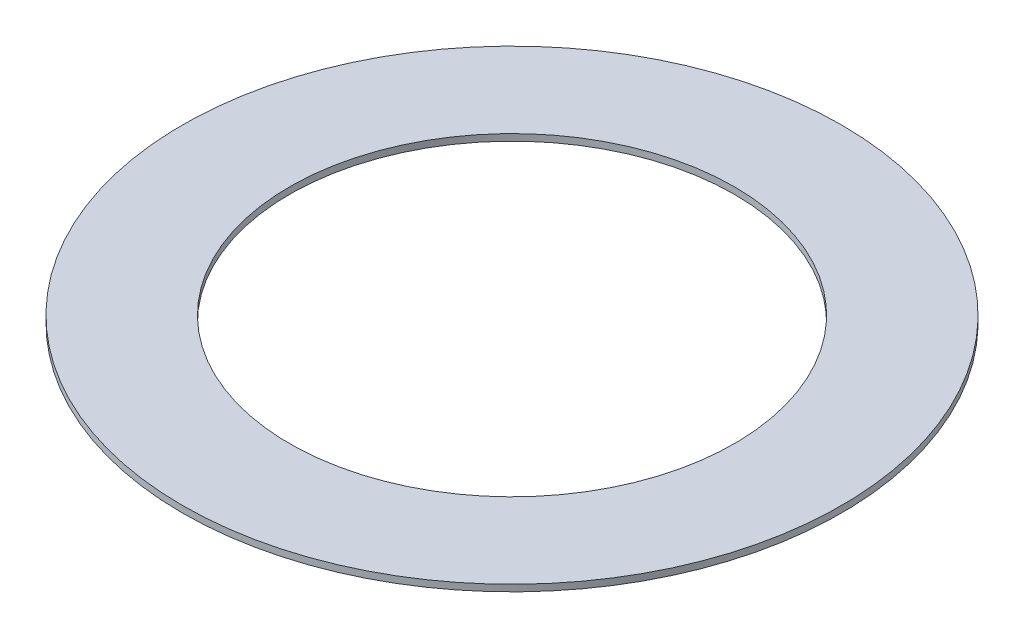
SolidWorks part; units mm, degrees
material "AISI 304"
ref_plane "前视基准面" through (0, 0, 0) normal (0, 0, 1) x (1, 0, 0)
ref_plane "上视基准面" through (0, 0, 0) normal (0, 1, 0) x (1, 0, 0)
ref_plane "右视基准面" through (0, 0, 0) normal (1, 0, 0) x (0, 0, -1)
sketch "草图1" plane through (0, 0, 0) normal (0, 0, 1) x (1, 0, 0)
  line L0 (10, 0.2) -> (6.75, 0.2)
  line L1 (6.75, 0.2) -> (6.75, 0)
  line L2 (6.75, 0) -> (10, 0)
  line L3 (10, 0) -> (10, 0.2)
  line L4 (0, 0.2) -> (0, 0) construction
revolve "旋转1" add sketch "草图1" angle 360 about L4 reverse direction yes
